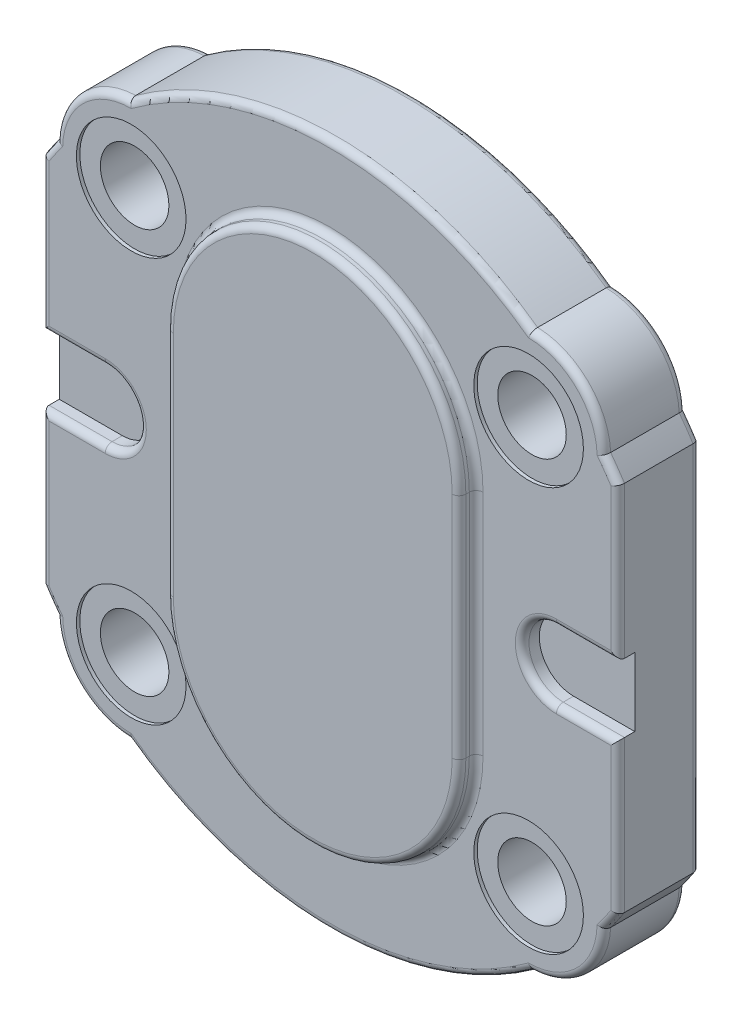
SolidWorks part; units mm, degrees
ref_plane "Front Plane" through (0, 0, 0) normal (0, 0, 1) x (1, 0, 0)
ref_plane "Top Plane" through (0, 0, 0) normal (0, 1, 0) x (1, 0, 0)
ref_plane "Right Plane" through (0, 0, 0) normal (1, 0, 0) x (0, 0, -1)
sketch "Sketch2" plane through (0, 0, 0) normal (0, 0, 1) x (1, 0, 0)
  line L0 (-87.8004, 0) -> (-42, 0) construction
  line L1 (0, -94.4364) -> (0, 94.4364) construction
  line L2 (42, 27.1293) -> (42, 5)
  line L3 (-42, 27.1293) -> (-42, 5)
  line L6 (42, -5) -> (42, -27.1293)
  line L10 (-42, -5) -> (-42, -27.1293)
  line L11 (-42, 5) -> (-42, -5)
  line L12 (42, 5) -> (42, -5)
  line L13 (42, 0) -> (87.8004, 0) construction
  arc A0 (-42, -27.1293) -> (-39.9879, -30.0161) centre (0, 0) ccw
  arc A1 (42, 27.1293) -> (39.9879, 30.0161) centre (0, 0) ccw
  circle A2 centre (29, 29.5) radius 5
  circle A3 centre (-29, 29.5) radius 5
  circle A4 centre (29, -29.5) radius 5
  circle A5 centre (-29, -29.5) radius 5
  arc A6 (39.9879, 30.0161) -> (29.3283, 40.4951) centre (29, 29.5) ccw
  arc A7 (29.3283, 40.4951) -> (-29.3283, 40.4951) centre (0, 0) ccw
  arc A8 (-39.9879, 30.0161) -> (-29.3283, 40.4951) centre (-29, 29.5) cw
  arc A9 (39.9879, -30.0161) -> (29.3283, -40.4951) centre (29, -29.5) cw
  arc A10 (-39.9879, -30.0161) -> (-29.3283, -40.4951) centre (-29, -29.5) ccw
  arc A11 (-29.3283, -40.4951) -> (29.3283, -40.4951) centre (0, 0) ccw
  arc A12 (39.9879, -30.0161) -> (42, -27.1293) centre (0, 0) ccw
  arc A13 (-39.9879, 30.0161) -> (-42, 27.1293) centre (0, 0) ccw
  point P6 (0, 0)
  point P9 (0, 0)
  dimension "D1" = 100
  dimension "D2" = 10
  dimension "D4" = 29
  dimension "D7" = 22
  dimension "D3" = 29.5
  dimension "D5" = 42
  dimension "D6" = 42
extrude "Boss-Extrude1" add sketch "Sketch2" along normal blind 12
sketch "Sketch3" plane through (0, 0, 12) normal (0, 0, 1) x (1, 0, 0)
  line L0 (-57.7589, 0) -> (-21.35, 0) construction
  line L1 (-21.35, 16.68) -> (-21.35, -16.68)
  line L2 (21.35, 16.68) -> (21.35, -16.68)
  line L3 (21.35, 0) -> (57.7589, 0) construction
  arc A0 (21.35, 16.68) -> (-21.35, 16.68) centre (0, 16.68) ccw
  arc A1 (-21.35, -16.68) -> (21.35, -16.68) centre (0, -16.68) ccw
  point P8 (0, 0)
  dimension "D1" = 42.7
  dimension "D2" = 42.7
  dimension "D3" = 16.68
  dimension "D4" = 16.68
extrude "Boss-Extrude2" add sketch "Sketch3" along normal blind 2.5
fillet "Fillet1" radius 1 8 edges at (0, 38.03, 12) (21.35, 0, 12) (0, -38.03, 12) (-21.35, 0, 12) (0, -38.03, 14.5) (21.35, 0, 14.5) (0, 38.03, 14.5) (-21.35, 0, 14.5)
sketch "Sketch8" plane through (0, 0, 12) normal (0, 0, 1) x (1, 0, 0)
  line L0 (-97.9813, 0) -> (97.9813, 0) construction
  line L1 (33.062, 5) -> (42, 5)
  line L2 (42, -27.1293) -> (42, 27.1293) construction
  line L3 (33.062, -5) -> (42, -5)
  line L4 (-32.7943, 5) -> (-42, 5)
  line L7 (-32.7943, -5) -> (-42, -5)
  line L10 (42, 5) -> (42, -5)
  line L11 (-42, 5) -> (-42, -5)
  arc A0 (33.062, 5) -> (33.062, -5) centre (33.062, 0) ccw
  arc A1 (-32.7943, -5) -> (-32.7943, 5) centre (-32.7943, 0) ccw
  point P4 (0, 0)
  dimension "D1" = 10
  dimension "D2" = 10
extrude "Cut-Extrude1" cut sketch "Sketch8" against normal blind 2.5
fillet "Fillet2" radius 1 32 edges at (41.0193, -28.5904, 12) (41.0193, -28.5904, 0) (36.7114, -37.3444, 0) (36.7114, -37.3444, 12) (0, -50, 0) (0, -50, 12) (-36.7114, -37.3444, 0) (-41.0193, -28.5904, 0) (-36.7114, -37.3444, 12) (-41.0193, -28.5904, 12) (-42, -16.0647, 12) (-42, 0, 0) (-42, 16.0647, 12) (-41.0193, 28.5904, 12) (-41.0193, 28.5904, 0) (-36.7114, 37.3444, 0) (36.7114, 37.3444, 0) (0, 50, 0) (37.531, 5, 12) (28.062, 0, 12) (37.531, -5, 12) (42, -16.0647, 12) (42, 16.0647, 12) (42, 0, 0) (36.7114, 37.3444, 12) (41.0193, 28.5904, 12) (41.0193, 28.5904, 0) (0, 50, 12) (-36.7114, 37.3444, 12) (-37.3971, 5, 12) (-37.3971, -5, 12) (-27.7943, 0, 12)
sketch "Sketch9" plane through (0, 0, 12) normal (0, 0, 1) x (1, 0, 0)
  circle A0 centre (29, 29.5) radius 8
  circle A1 centre (29, -29.5) radius 8
  circle A2 centre (-29, -29.5) radius 8
  circle A3 centre (-29, 29.5) radius 8
  dimension "D1" = 16
extrude "Cut-Extrude2" cut sketch "Sketch9" against normal blind 0.5
sketch "Sketch11" plane through (0, 0, 0) normal (1, 0, 0) x (0, 0, -1)
  line L2 (-1, -27.1293) -> (-1, 27.1293) construction
  line L3 (-1, 2) -> (0, 2)
  line L4 (0, 26.8328) -> (0, -26.8328) construction
  line L5 (-2, 0) -> (-1, 2)
  line L6 (0, 2) -> (0, 0)
  line L7 (0, 0) -> (-2, 0) construction
  line L8 (0, 0) -> (-2, 0)
revolve "Cut-Revolve1" cut sketch "Sketch11" angle 360 about L7
